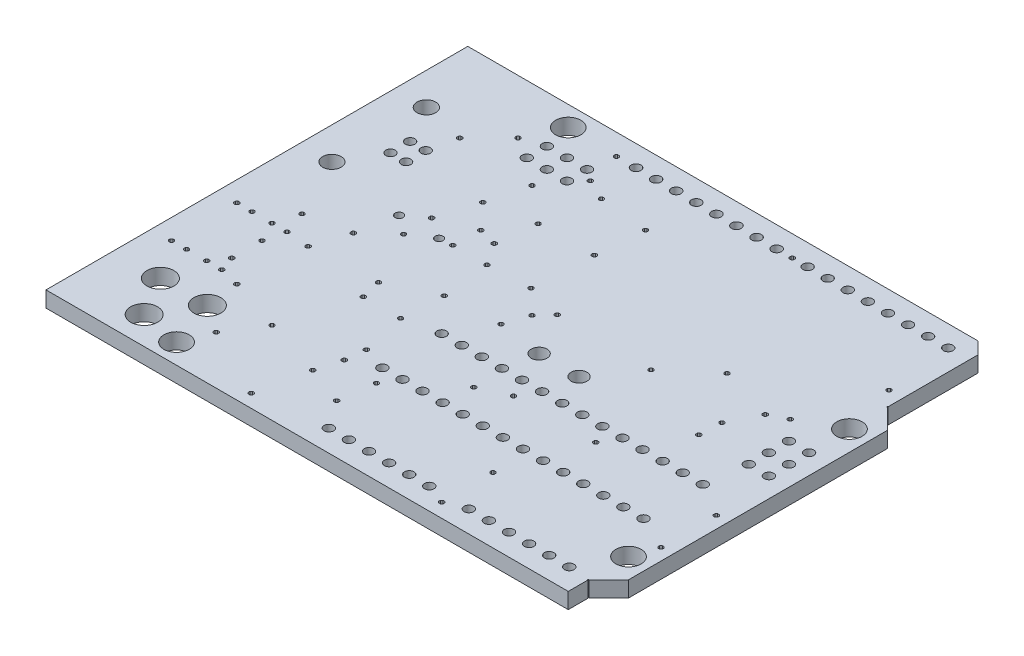
SolidWorks part; units mm, degrees
material "Fibra de vidrio-A"
ref_plane "Alzado" through (0, 0, 0) normal (0, 0, 1) x (1, 0, 0)
ref_plane "Planta" through (0, 0, 0) normal (0, 1, 0) x (1, 0, 0)
ref_plane "Vista lateral" through (0, 0, 0) normal (1, 0, 0) x (0, 0, -1)
sketch "Croquis1" plane through (0, 0, 0) normal (0, 1, 0) x (1, 0, 0)
  line L0 (0, 53.34) -> (64.516, 53.34)
  line L1 (64.516, 53.34) -> (66.04, 51.816)
  line L2 (66.04, 40.386) -> (68.58, 37.846)
  line L3 (68.58, 37.846) -> (68.58, 5.08)
  line L4 (68.58, 5.08) -> (66.04, 2.54)
  line L5 (66.04, 2.54) -> (66.04, 0)
  line L6 (66.04, 0) -> (0, 0)
  line L7 (0, 0) -> (0, 53.34)
  line L8 (66.04, 51.816) -> (66.04, 40.386)
  line L9 (30.8356, 10.5522) -> (30.8356, 10.7838)
  line L10 (30.8356, 10.7838) -> (30.9992, 10.9474)
  line L11 (30.9992, 10.9474) -> (31.2308, 10.9474)
  line L12 (31.2308, 10.9474) -> (31.3944, 10.7838)
  line L13 (31.3944, 10.7838) -> (31.3944, 10.5522)
  line L14 (31.3944, 10.5522) -> (31.2308, 10.3886)
  line L15 (31.2308, 10.3886) -> (30.9992, 10.3886)
  line L16 (30.9992, 10.3886) -> (30.8356, 10.5522)
  line L18 (25.2476, 19.1882) -> (25.2476, 19.4198)
  line L19 (25.2476, 19.4198) -> (25.4112, 19.5834)
  line L20 (25.4112, 19.5834) -> (25.6428, 19.5834)
  line L21 (25.6428, 19.5834) -> (25.8064, 19.4198)
  line L22 (25.8064, 19.4198) -> (25.8064, 19.1882)
  line L23 (25.8064, 19.1882) -> (25.6428, 19.0246)
  line L24 (25.6428, 19.0246) -> (25.4112, 19.0246)
  line L25 (25.4112, 19.0246) -> (25.2476, 19.1882)
  line L27 (7.5946, 24.3952) -> (7.5946, 24.6268)
  line L28 (7.5946, 24.6268) -> (7.7582, 24.7904)
  line L29 (7.7582, 24.7904) -> (7.9898, 24.7904)
  line L30 (7.9898, 24.7904) -> (8.1534, 24.6268)
  line L31 (8.1534, 24.6268) -> (8.1534, 24.3952)
  line L32 (8.1534, 24.3952) -> (7.9898, 24.2316)
  line L33 (7.9898, 24.2316) -> (7.7582, 24.2316)
  line L34 (7.7582, 24.2316) -> (7.5946, 24.3952)
  line L36 (26.2636, 11.0602) -> (26.2636, 11.2918)
  line L37 (26.2636, 11.2918) -> (26.4272, 11.4554)
  line L38 (26.4272, 11.4554) -> (26.6588, 11.4554)
  line L39 (26.6588, 11.4554) -> (26.8224, 11.2918)
  line L40 (26.8224, 11.2918) -> (26.8224, 11.0602)
  line L41 (26.8224, 11.0602) -> (26.6588, 10.8966)
  line L42 (26.6588, 10.8966) -> (26.4272, 10.8966)
  line L43 (26.4272, 10.8966) -> (26.2636, 11.0602)
  line L45 (17.8816, 10.2982) -> (17.8816, 10.5298)
  line L46 (17.8816, 10.5298) -> (18.0452, 10.6934)
  line L47 (18.0452, 10.6934) -> (18.2768, 10.6934)
  line L48 (18.2768, 10.6934) -> (18.4404, 10.5298)
  line L49 (18.4404, 10.5298) -> (18.4404, 10.2982)
  line L50 (18.4404, 10.2982) -> (18.2768, 10.1346)
  line L51 (18.2768, 10.1346) -> (18.0452, 10.1346)
  line L52 (18.0452, 10.1346) -> (17.8816, 10.2982)
  line L54 (2.2606, 21.4742) -> (2.2606, 21.7058)
  line L55 (2.2606, 21.7058) -> (2.4242, 21.8694)
  line L56 (2.4242, 21.8694) -> (2.6558, 21.8694)
  line L57 (2.6558, 21.8694) -> (2.8194, 21.7058)
  line L58 (2.8194, 21.7058) -> (2.8194, 21.4742)
  line L59 (2.8194, 21.4742) -> (2.6558, 21.3106)
  line L60 (2.6558, 21.3106) -> (2.4242, 21.3106)
  line L61 (2.4242, 21.3106) -> (2.2606, 21.4742)
  line L63 (4.1656, 21.4742) -> (4.1656, 21.7058)
  line L64 (4.1656, 21.7058) -> (4.3292, 21.8694)
  line L65 (4.3292, 21.8694) -> (4.5608, 21.8694)
  line L66 (4.5608, 21.8694) -> (4.7244, 21.7058)
  line L67 (4.7244, 21.7058) -> (4.7244, 21.4742)
  line L68 (4.7244, 21.4742) -> (4.5608, 21.3106)
  line L69 (4.5608, 21.3106) -> (4.3292, 21.3106)
  line L70 (4.3292, 21.3106) -> (4.1656, 21.4742)
  line L72 (6.7056, 21.4742) -> (6.7056, 21.7058)
  line L73 (6.7056, 21.7058) -> (6.8692, 21.8694)
  line L74 (6.8692, 21.8694) -> (7.1008, 21.8694)
  line L75 (7.1008, 21.8694) -> (7.2644, 21.7058)
  line L76 (7.2644, 21.7058) -> (7.2644, 21.4742)
  line L77 (7.2644, 21.4742) -> (7.1008, 21.3106)
  line L78 (7.1008, 21.3106) -> (6.8692, 21.3106)
  line L79 (6.8692, 21.3106) -> (6.7056, 21.4742)
  line L81 (8.6106, 21.4742) -> (8.6106, 21.7058)
  line L82 (8.6106, 21.7058) -> (8.7742, 21.8694)
  line L83 (8.7742, 21.8694) -> (9.0058, 21.8694)
  line L84 (9.0058, 21.8694) -> (9.1694, 21.7058)
  line L85 (9.1694, 21.7058) -> (9.1694, 21.4742)
  line L86 (9.1694, 21.4742) -> (9.0058, 21.3106)
  line L87 (9.0058, 21.3106) -> (8.7742, 21.3106)
  line L88 (8.7742, 21.3106) -> (8.6106, 21.4742)
  line L90 (2.2606, 13.2192) -> (2.2606, 13.4508)
  line L91 (2.2606, 13.4508) -> (2.4242, 13.6144)
  line L92 (2.4242, 13.6144) -> (2.6558, 13.6144)
  line L93 (2.6558, 13.6144) -> (2.8194, 13.4508)
  line L94 (2.8194, 13.4508) -> (2.8194, 13.2192)
  line L95 (2.8194, 13.2192) -> (2.6558, 13.0556)
  line L96 (2.6558, 13.0556) -> (2.4242, 13.0556)
  line L97 (2.4242, 13.0556) -> (2.2606, 13.2192)
  line L99 (4.1656, 13.2192) -> (4.1656, 13.4508)
  line L100 (4.1656, 13.4508) -> (4.3292, 13.6144)
  line L101 (4.3292, 13.6144) -> (4.5608, 13.6144)
  line L102 (4.5608, 13.6144) -> (4.7244, 13.4508)
  line L103 (4.7244, 13.4508) -> (4.7244, 13.2192)
  line L104 (4.7244, 13.2192) -> (4.5608, 13.0556)
  line L105 (4.5608, 13.0556) -> (4.3292, 13.0556)
  line L106 (4.3292, 13.0556) -> (4.1656, 13.2192)
  line L108 (6.7056, 13.2192) -> (6.7056, 13.4508)
  line L109 (6.7056, 13.4508) -> (6.8692, 13.6144)
  line L110 (6.8692, 13.6144) -> (7.1008, 13.6144)
  line L111 (7.1008, 13.6144) -> (7.2644, 13.4508)
  line L112 (7.2644, 13.4508) -> (7.2644, 13.2192)
  line L113 (7.2644, 13.2192) -> (7.1008, 13.0556)
  line L114 (7.1008, 13.0556) -> (6.8692, 13.0556)
  line L115 (6.8692, 13.0556) -> (6.7056, 13.2192)
  line L117 (8.6106, 13.2192) -> (8.6106, 13.4508)
  line L118 (8.6106, 13.4508) -> (8.7742, 13.6144)
  line L119 (8.7742, 13.6144) -> (9.0058, 13.6144)
  line L120 (9.0058, 13.6144) -> (9.1694, 13.4508)
  line L121 (9.1694, 13.4508) -> (9.1694, 13.2192)
  line L122 (9.1694, 13.2192) -> (9.0058, 13.0556)
  line L123 (9.0058, 13.0556) -> (8.7742, 13.0556)
  line L124 (8.7742, 13.0556) -> (8.6106, 13.2192)
  line L126 (7.9756, 15.1242) -> (7.9756, 15.3558)
  line L127 (7.9756, 15.3558) -> (8.1392, 15.5194)
  line L128 (8.1392, 15.5194) -> (8.3708, 15.5194)
  line L129 (8.3708, 15.5194) -> (8.5344, 15.3558)
  line L130 (8.5344, 15.3558) -> (8.5344, 15.1242)
  line L131 (8.5344, 15.1242) -> (8.3708, 14.9606)
  line L132 (8.3708, 14.9606) -> (8.1392, 14.9606)
  line L133 (8.1392, 14.9606) -> (7.9756, 15.1242)
  line L135 (7.9756, 18.9342) -> (7.9756, 19.1658)
  line L136 (7.9756, 19.1658) -> (8.1392, 19.3294)
  line L137 (8.1392, 19.3294) -> (8.3708, 19.3294)
  line L138 (8.3708, 19.3294) -> (8.5344, 19.1658)
  line L139 (8.5344, 19.1658) -> (8.5344, 18.9342)
  line L140 (8.5344, 18.9342) -> (8.3708, 18.7706)
  line L141 (8.3708, 18.7706) -> (8.1392, 18.7706)
  line L142 (8.1392, 18.7706) -> (7.9756, 18.9342)
  line L144 (20.6756, 33.9202) -> (20.6756, 34.1518)
  line L145 (20.6756, 34.1518) -> (20.8392, 34.3154)
  line L146 (20.8392, 34.3154) -> (21.0708, 34.3154)
  line L147 (21.0708, 34.3154) -> (21.2344, 34.1518)
  line L148 (21.2344, 34.1518) -> (21.2344, 33.9202)
  line L149 (21.2344, 33.9202) -> (21.0708, 33.7566)
  line L150 (21.0708, 33.7566) -> (20.8392, 33.7566)
  line L151 (20.8392, 33.7566) -> (20.6756, 33.9202)
  line L153 (24.8666, 44.9692) -> (24.8666, 45.2008)
  line L154 (24.8666, 45.2008) -> (25.0302, 45.3644)
  line L155 (25.0302, 45.3644) -> (25.2618, 45.3644)
  line L156 (25.2618, 45.3644) -> (25.4254, 45.2008)
  line L157 (25.4254, 45.2008) -> (25.4254, 44.9692)
  line L158 (25.4254, 44.9692) -> (25.2618, 44.8056)
  line L159 (25.2618, 44.8056) -> (25.0302, 44.8056)
  line L160 (25.0302, 44.8056) -> (24.8666, 44.9692)
  line L162 (23.5966, 38.2382) -> (23.5966, 38.4698)
  line L163 (23.5966, 38.4698) -> (23.7602, 38.6334)
  line L164 (23.7602, 38.6334) -> (23.9918, 38.6334)
  line L165 (23.9918, 38.6334) -> (24.1554, 38.4698)
  line L166 (24.1554, 38.4698) -> (24.1554, 38.2382)
  line L167 (24.1554, 38.2382) -> (23.9918, 38.0746)
  line L168 (23.9918, 38.0746) -> (23.7602, 38.0746)
  line L169 (23.7602, 38.0746) -> (23.5966, 38.2382)
  line L171 (24.8666, 30.4912) -> (24.8666, 30.7228)
  line L172 (24.8666, 30.7228) -> (25.0302, 30.8864)
  line L173 (25.0302, 30.8864) -> (25.2618, 30.8864)
  line L174 (25.2618, 30.8864) -> (25.4254, 30.7228)
  line L175 (25.4254, 30.7228) -> (25.4254, 30.4912)
  line L176 (25.4254, 30.4912) -> (25.2618, 30.3276)
  line L177 (25.2618, 30.3276) -> (25.0302, 30.3276)
  line L178 (25.0302, 30.3276) -> (24.8666, 30.4912)
  line L180 (20.5486, 19.1882) -> (20.5486, 19.4198)
  line L181 (20.5486, 19.4198) -> (20.7122, 19.5834)
  line L182 (20.7122, 19.5834) -> (20.9438, 19.5834)
  line L183 (20.9438, 19.5834) -> (21.1074, 19.4198)
  line L184 (21.1074, 19.4198) -> (21.1074, 19.1882)
  line L185 (21.1074, 19.1882) -> (20.9438, 19.0246)
  line L186 (20.9438, 19.0246) -> (20.7122, 19.0246)
  line L187 (20.7122, 19.0246) -> (20.5486, 19.1882)
  line L189 (11.5316, 21.2202) -> (11.5316, 21.4518)
  line L190 (11.5316, 21.4518) -> (11.6952, 21.6154)
  line L191 (11.6952, 21.6154) -> (11.9268, 21.6154)
  line L192 (11.9268, 21.6154) -> (12.0904, 21.4518)
  line L193 (12.0904, 21.4518) -> (12.0904, 21.2202)
  line L194 (12.0904, 21.2202) -> (11.9268, 21.0566)
  line L195 (11.9268, 21.0566) -> (11.6952, 21.0566)
  line L196 (11.6952, 21.0566) -> (11.5316, 21.2202)
  line L198 (30.226, 6.1326) -> (30.226, 6.3642)
  line L199 (30.226, 6.3642) -> (30.3896, 6.5278)
  line L200 (30.3896, 6.5278) -> (30.6212, 6.5278)
  line L201 (30.6212, 6.5278) -> (30.7848, 6.3642)
  line L202 (30.7848, 6.3642) -> (30.7848, 6.1326)
  line L203 (30.7848, 6.1326) -> (30.6212, 5.969)
  line L204 (30.6212, 5.969) -> (30.3896, 5.969)
  line L205 (30.3896, 5.969) -> (30.226, 6.1326)
  line L207 (26.5176, 13.6002) -> (26.5176, 13.8318)
  line L208 (26.5176, 13.8318) -> (26.6812, 13.9954)
  line L209 (26.6812, 13.9954) -> (26.9128, 13.9954)
  line L210 (26.9128, 13.9954) -> (27.0764, 13.8318)
  line L211 (27.0764, 13.8318) -> (27.0764, 13.6002)
  line L212 (27.0764, 13.6002) -> (26.9128, 13.4366)
  line L213 (26.9128, 13.4366) -> (26.6812, 13.4366)
  line L214 (26.6812, 13.4366) -> (26.5176, 13.6002)
  line L216 (17.7546, 37.0952) -> (17.7546, 37.3268)
  line L217 (17.7546, 37.3268) -> (17.9182, 37.4904)
  line L218 (17.9182, 37.4904) -> (18.1498, 37.4904)
  line L219 (18.1498, 37.4904) -> (18.3134, 37.3268)
  line L220 (18.3134, 37.3268) -> (18.3134, 37.0952)
  line L221 (18.3134, 37.0952) -> (18.1498, 36.9316)
  line L222 (18.1498, 36.9316) -> (17.9182, 36.9316)
  line L223 (17.9182, 36.9316) -> (17.7546, 37.0952)
  line L225 (20.5486, 30.4912) -> (20.5486, 30.7228)
  line L226 (20.5486, 30.7228) -> (20.7122, 30.8864)
  line L227 (20.7122, 30.8864) -> (20.9438, 30.8864)
  line L228 (20.9438, 30.8864) -> (21.1074, 30.7228)
  line L229 (21.1074, 30.7228) -> (21.1074, 30.4912)
  line L230 (21.1074, 30.4912) -> (20.9438, 30.3276)
  line L231 (20.9438, 30.3276) -> (20.7122, 30.3276)
  line L232 (20.7122, 30.3276) -> (20.5486, 30.4912)
  line L234 (15.113, 6.0056) -> (15.113, 6.2372)
  line L235 (15.113, 6.2372) -> (15.2766, 6.4008)
  line L236 (15.2766, 6.4008) -> (15.5082, 6.4008)
  line L237 (15.5082, 6.4008) -> (15.6718, 6.2372)
  line L238 (15.6718, 6.2372) -> (15.6718, 6.0056)
  line L239 (15.6718, 6.0056) -> (15.5082, 5.842)
  line L240 (15.5082, 5.842) -> (15.2766, 5.842)
  line L241 (15.2766, 5.842) -> (15.113, 6.0056)
  line L243 (22.987, 33.3106) -> (22.987, 33.5422)
  line L244 (22.987, 33.5422) -> (23.1506, 33.7058)
  line L245 (23.1506, 33.7058) -> (23.3822, 33.7058)
  line L246 (23.3822, 33.7058) -> (23.5458, 33.5422)
  line L247 (23.5458, 33.5422) -> (23.5458, 33.3106)
  line L248 (23.5458, 33.3106) -> (23.3822, 33.147)
  line L249 (23.3822, 33.147) -> (23.1506, 33.147)
  line L250 (23.1506, 33.147) -> (22.987, 33.3106)
  line L252 (51.9176, 33.7932) -> (51.9176, 34.0248)
  line L253 (51.9176, 34.0248) -> (52.0812, 34.1884)
  line L254 (52.0812, 34.1884) -> (52.3128, 34.1884)
  line L255 (52.3128, 34.1884) -> (52.4764, 34.0248)
  line L256 (52.4764, 34.0248) -> (52.4764, 33.7932)
  line L257 (52.4764, 33.7932) -> (52.3128, 33.6296)
  line L258 (52.3128, 33.6296) -> (52.0812, 33.6296)
  line L259 (52.0812, 33.6296) -> (51.9176, 33.7932)
  line L261 (30.5816, 38.3652) -> (30.5816, 38.5968)
  line L262 (30.5816, 38.5968) -> (30.7452, 38.7604)
  line L263 (30.7452, 38.7604) -> (30.9768, 38.7604)
  line L264 (30.9768, 38.7604) -> (31.1404, 38.5968)
  line L265 (31.1404, 38.5968) -> (31.1404, 38.3652)
  line L266 (31.1404, 38.3652) -> (30.9768, 38.2016)
  line L267 (30.9768, 38.2016) -> (30.7452, 38.2016)
  line L268 (30.7452, 38.2016) -> (30.5816, 38.3652)
  line L270 (11.1506, 12.5842) -> (11.1506, 12.8158)
  line L271 (11.1506, 12.8158) -> (11.3142, 12.9794)
  line L272 (11.3142, 12.9794) -> (11.5458, 12.9794)
  line L273 (11.5458, 12.9794) -> (11.7094, 12.8158)
  line L274 (11.7094, 12.8158) -> (11.7094, 12.5842)
  line L275 (11.7094, 12.5842) -> (11.5458, 12.4206)
  line L276 (11.5458, 12.4206) -> (11.3142, 12.4206)
  line L277 (11.3142, 12.4206) -> (11.1506, 12.5842)
  line L279 (40.894, 17.8166) -> (40.894, 18.0482)
  line L280 (40.894, 18.0482) -> (41.0576, 18.2118)
  line L281 (41.0576, 18.2118) -> (41.2892, 18.2118)
  line L282 (41.2892, 18.2118) -> (41.4528, 18.0482)
  line L283 (41.4528, 18.0482) -> (41.4528, 17.8166)
  line L284 (41.4528, 17.8166) -> (41.2892, 17.653)
  line L285 (41.2892, 17.653) -> (41.0576, 17.653)
  line L286 (41.0576, 17.653) -> (40.894, 17.8166)
  line L288 (51.181, 17.9436) -> (51.181, 18.1752)
  line L289 (51.181, 18.1752) -> (51.3446, 18.3388)
  line L290 (51.3446, 18.3388) -> (51.5762, 18.3388)
  line L291 (51.5762, 18.3388) -> (51.7398, 18.1752)
  line L292 (51.7398, 18.1752) -> (51.7398, 17.9436)
  line L293 (51.7398, 17.9436) -> (51.5762, 17.78)
  line L294 (51.5762, 17.78) -> (51.3446, 17.78)
  line L295 (51.3446, 17.78) -> (51.181, 17.9436)
  line L297 (30.2006, 30.7452) -> (30.2006, 30.9768)
  line L298 (30.2006, 30.9768) -> (30.3642, 31.1404)
  line L299 (30.3642, 31.1404) -> (30.5958, 31.1404)
  line L300 (30.5958, 31.1404) -> (30.7594, 30.9768)
  line L301 (30.7594, 30.9768) -> (30.7594, 30.7452)
  line L302 (30.7594, 30.7452) -> (30.5958, 30.5816)
  line L303 (30.5958, 30.5816) -> (30.3642, 30.5816)
  line L304 (30.3642, 30.5816) -> (30.2006, 30.7452)
  line L306 (43.4086, 50.5572) -> (43.4086, 50.7888)
  line L307 (43.4086, 50.7888) -> (43.5722, 50.9524)
  line L308 (43.5722, 50.9524) -> (43.8038, 50.9524)
  line L309 (43.8038, 50.9524) -> (43.9674, 50.7888)
  line L310 (43.9674, 50.7888) -> (43.9674, 50.5572)
  line L311 (43.9674, 50.5572) -> (43.8038, 50.3936)
  line L312 (43.8038, 50.3936) -> (43.5722, 50.3936)
  line L313 (43.5722, 50.3936) -> (43.4086, 50.5572)
  line L315 (47.9806, 1.6622) -> (47.9806, 1.8938)
  line L316 (47.9806, 1.8938) -> (48.1442, 2.0574)
  line L317 (48.1442, 2.0574) -> (48.3758, 2.0574)
  line L318 (48.3758, 2.0574) -> (48.5394, 1.8938)
  line L319 (48.5394, 1.8938) -> (48.5394, 1.6622)
  line L320 (48.5394, 1.6622) -> (48.3758, 1.4986)
  line L321 (48.3758, 1.4986) -> (48.1442, 1.4986)
  line L322 (48.1442, 1.4986) -> (47.9806, 1.6622)
  line L324 (16.2306, 28.5862) -> (16.2306, 28.8178)
  line L325 (16.2306, 28.8178) -> (16.3942, 28.9814)
  line L326 (16.3942, 28.9814) -> (16.6258, 28.9814)
  line L327 (16.6258, 28.9814) -> (16.7894, 28.8178)
  line L328 (16.7894, 28.8178) -> (16.7894, 28.5862)
  line L329 (16.7894, 28.5862) -> (16.6258, 28.4226)
  line L330 (16.6258, 28.4226) -> (16.3942, 28.4226)
  line L331 (16.3942, 28.4226) -> (16.2306, 28.5862)
  line L333 (56.9976, 28.0782) -> (56.9976, 28.3098)
  line L334 (56.9976, 28.3098) -> (57.1612, 28.4734)
  line L335 (57.1612, 28.4734) -> (57.3928, 28.4734)
  line L336 (57.3928, 28.4734) -> (57.5564, 28.3098)
  line L337 (57.5564, 28.3098) -> (57.5564, 28.0782)
  line L338 (57.5564, 28.0782) -> (57.3928, 27.9146)
  line L339 (57.3928, 27.9146) -> (57.1612, 27.9146)
  line L340 (57.1612, 27.9146) -> (56.9976, 28.0782)
  line L342 (24.003, 1.5606) -> (24.003, 1.7922)
  line L343 (24.003, 1.7922) -> (24.1666, 1.9558)
  line L344 (24.1666, 1.9558) -> (24.3982, 1.9558)
  line L345 (24.3982, 1.9558) -> (24.5618, 1.7922)
  line L346 (24.5618, 1.7922) -> (24.5618, 1.5606)
  line L347 (24.5618, 1.5606) -> (24.3982, 1.397)
  line L348 (24.3982, 1.397) -> (24.1666, 1.397)
  line L349 (24.1666, 1.397) -> (24.003, 1.5606)
  line L351 (66.802, 10.5776) -> (66.802, 10.8092)
  line L352 (66.802, 10.8092) -> (66.9656, 10.9728)
  line L353 (66.9656, 10.9728) -> (67.1972, 10.9728)
  line L354 (67.1972, 10.9728) -> (67.3608, 10.8092)
  line L355 (67.3608, 10.8092) -> (67.3608, 10.5776)
  line L356 (67.3608, 10.5776) -> (67.1972, 10.414)
  line L357 (67.1972, 10.414) -> (66.9656, 10.414)
  line L358 (66.9656, 10.414) -> (66.802, 10.5776)
  line L360 (64.008, 42.2006) -> (64.008, 42.4322)
  line L361 (64.008, 42.4322) -> (64.1716, 42.5958)
  line L362 (64.1716, 42.5958) -> (64.4032, 42.5958)
  line L363 (64.4032, 42.5958) -> (64.5668, 42.4322)
  line L364 (64.5668, 42.4322) -> (64.5668, 42.2006)
  line L365 (64.5668, 42.2006) -> (64.4032, 42.037)
  line L366 (64.4032, 42.037) -> (64.1716, 42.037)
  line L367 (64.1716, 42.037) -> (64.008, 42.2006)
  line L369 (12.9286, 25.5382) -> (12.9286, 25.7698)
  line L370 (12.9286, 25.7698) -> (13.0922, 25.9334)
  line L371 (13.0922, 25.9334) -> (13.3238, 25.9334)
  line L372 (13.3238, 25.9334) -> (13.4874, 25.7698)
  line L373 (13.4874, 25.7698) -> (13.4874, 25.5382)
  line L374 (13.4874, 25.5382) -> (13.3238, 25.3746)
  line L375 (13.3238, 25.3746) -> (13.0922, 25.3746)
  line L376 (13.0922, 25.3746) -> (12.9286, 25.5382)
  line L378 (66.802, 17.5626) -> (66.802, 17.7942)
  line L379 (66.802, 17.7942) -> (66.9656, 17.9578)
  line L380 (66.9656, 17.9578) -> (67.1972, 17.9578)
  line L381 (67.1972, 17.9578) -> (67.3608, 17.7942)
  line L382 (67.3608, 17.7942) -> (67.3608, 17.5626)
  line L383 (67.3608, 17.5626) -> (67.1972, 17.399)
  line L384 (67.1972, 17.399) -> (66.9656, 17.399)
  line L385 (66.9656, 17.399) -> (66.802, 17.5626)
  line L387 (19.9136, 21.7282) -> (19.9136, 21.9598)
  line L388 (19.9136, 21.9598) -> (20.0772, 22.1234)
  line L389 (20.0772, 22.1234) -> (20.3088, 22.1234)
  line L390 (20.3088, 22.1234) -> (20.4724, 21.9598)
  line L391 (20.4724, 21.9598) -> (20.4724, 21.7282)
  line L392 (20.4724, 21.7282) -> (20.3088, 21.5646)
  line L393 (20.3088, 21.5646) -> (20.0772, 21.5646)
  line L394 (20.0772, 21.5646) -> (19.9136, 21.7282)
  line L396 (12.9286, 46.3662) -> (12.9286, 46.5978)
  line L397 (12.9286, 46.5978) -> (13.0922, 46.7614)
  line L398 (13.0922, 46.7614) -> (13.3238, 46.7614)
  line L399 (13.3238, 46.7614) -> (13.4874, 46.5978)
  line L400 (13.4874, 46.5978) -> (13.4874, 46.3662)
  line L401 (13.4874, 46.3662) -> (13.3238, 46.2026)
  line L402 (13.3238, 46.2026) -> (13.0922, 46.2026)
  line L403 (13.0922, 46.2026) -> (12.9286, 46.3662)
  line L405 (21.1836, 50.5572) -> (21.1836, 50.7888)
  line L406 (21.1836, 50.7888) -> (21.3472, 50.9524)
  line L407 (21.3472, 50.9524) -> (21.5788, 50.9524)
  line L408 (21.5788, 50.9524) -> (21.7424, 50.7888)
  line L409 (21.7424, 50.7888) -> (21.7424, 50.5572)
  line L410 (21.7424, 50.5572) -> (21.5788, 50.3936)
  line L411 (21.5788, 50.3936) -> (21.3472, 50.3936)
  line L412 (21.3472, 50.3936) -> (21.1836, 50.5572)
  line L414 (46.736, 29.3736) -> (46.736, 29.6052)
  line L415 (46.736, 29.6052) -> (46.8996, 29.7688)
  line L416 (46.8996, 29.7688) -> (47.1312, 29.7688)
  line L417 (47.1312, 29.7688) -> (47.2948, 29.6052)
  line L418 (47.2948, 29.6052) -> (47.2948, 29.3736)
  line L419 (47.2948, 29.3736) -> (47.1312, 29.21)
  line L420 (47.1312, 29.21) -> (46.8996, 29.21)
  line L421 (46.8996, 29.21) -> (46.736, 29.3736)
  line L423 (16.2306, 32.1422) -> (16.2306, 32.3738)
  line L424 (16.2306, 32.3738) -> (16.3942, 32.5374)
  line L425 (16.3942, 32.5374) -> (16.6258, 32.5374)
  line L426 (16.6258, 32.5374) -> (16.7894, 32.3738)
  line L427 (16.7894, 32.3738) -> (16.7894, 32.1422)
  line L428 (16.7894, 32.1422) -> (16.6258, 31.9786)
  line L429 (16.6258, 31.9786) -> (16.3942, 31.9786)
  line L430 (16.3942, 31.9786) -> (16.2306, 32.1422)
  line L432 (60.9346, 32.7772) -> (60.9346, 33.0088)
  line L433 (60.9346, 33.0088) -> (61.0982, 33.1724)
  line L434 (61.0982, 33.1724) -> (61.3298, 33.1724)
  line L435 (61.3298, 33.1724) -> (61.4934, 33.0088)
  line L436 (61.4934, 33.0088) -> (61.4934, 32.7772)
  line L437 (61.4934, 32.7772) -> (61.3298, 32.6136)
  line L438 (61.3298, 32.6136) -> (61.0982, 32.6136)
  line L439 (61.0982, 32.6136) -> (60.9346, 32.7772)
  line L441 (58.8518, 31.7104) -> (58.8518, 31.942)
  line L442 (58.8518, 31.942) -> (59.0154, 32.1056)
  line L443 (59.0154, 32.1056) -> (59.247, 32.1056)
  line L444 (59.247, 32.1056) -> (59.4106, 31.942)
  line L445 (59.4106, 31.942) -> (59.4106, 31.7104)
  line L446 (59.4106, 31.7104) -> (59.247, 31.5468)
  line L447 (59.247, 31.5468) -> (59.0154, 31.5468)
  line L448 (59.0154, 31.5468) -> (58.8518, 31.7104)
  line L450 (32.2326, 24.9032) -> (32.2326, 25.1348)
  line L451 (32.2326, 25.1348) -> (32.3962, 25.2984)
  line L452 (32.3962, 25.2984) -> (32.6278, 25.2984)
  line L453 (32.6278, 25.2984) -> (32.7914, 25.1348)
  line L454 (32.7914, 25.1348) -> (32.7914, 24.9032)
  line L455 (32.7914, 24.9032) -> (32.6278, 24.7396)
  line L456 (32.6278, 24.7396) -> (32.3962, 24.7396)
  line L457 (32.3962, 24.7396) -> (32.2326, 24.9032)
  line L459 (37.4396, 16.2672) -> (37.4396, 16.4988)
  line L460 (37.4396, 16.4988) -> (37.6032, 16.6624)
  line L461 (37.6032, 16.6624) -> (37.8348, 16.6624)
  line L462 (37.8348, 16.6624) -> (37.9984, 16.4988)
  line L463 (37.9984, 16.4988) -> (37.9984, 16.2672)
  line L464 (37.9984, 16.2672) -> (37.8348, 16.1036)
  line L465 (37.8348, 16.1036) -> (37.6032, 16.1036)
  line L466 (37.6032, 16.1036) -> (37.4396, 16.2672)
  line L468 (19.0246, 42.0482) -> (19.0246, 42.2798)
  line L469 (19.0246, 42.2798) -> (19.1882, 42.4434)
  line L470 (19.1882, 42.4434) -> (19.4198, 42.4434)
  line L471 (19.4198, 42.4434) -> (19.5834, 42.2798)
  line L472 (19.5834, 42.2798) -> (19.5834, 42.0482)
  line L473 (19.5834, 42.0482) -> (19.4198, 41.8846)
  line L474 (19.4198, 41.8846) -> (19.1882, 41.8846)
  line L475 (19.1882, 41.8846) -> (19.0246, 42.0482)
  line L477 (34.7726, 29.4752) -> (34.7726, 29.7068)
  line L478 (34.7726, 29.7068) -> (34.9362, 29.8704)
  line L479 (34.9362, 29.8704) -> (35.1678, 29.8704)
  line L480 (35.1678, 29.8704) -> (35.3314, 29.7068)
  line L481 (35.3314, 29.7068) -> (35.3314, 29.4752)
  line L482 (35.3314, 29.4752) -> (35.1678, 29.3116)
  line L483 (35.1678, 29.3116) -> (34.9362, 29.3116)
  line L484 (34.9362, 29.3116) -> (34.7726, 29.4752)
  line L486 (56.8706, 25.2842) -> (56.8706, 25.5158)
  line L487 (56.8706, 25.5158) -> (57.0342, 25.6794)
  line L488 (57.0342, 25.6794) -> (57.2658, 25.6794)
  line L489 (57.2658, 25.6794) -> (57.4294, 25.5158)
  line L490 (57.4294, 25.5158) -> (57.4294, 25.2842)
  line L491 (57.4294, 25.2842) -> (57.2658, 25.1206)
  line L492 (57.2658, 25.1206) -> (57.0342, 25.1206)
  line L493 (57.0342, 25.1206) -> (56.8706, 25.2842)
  line L495 (25.5524, 24.4206) -> (25.5524, 24.6522)
  line L496 (25.5524, 24.6522) -> (25.716, 24.8158)
  line L497 (25.716, 24.8158) -> (25.9476, 24.8158)
  line L498 (25.9476, 24.8158) -> (26.1112, 24.6522)
  line L499 (26.1112, 24.6522) -> (26.1112, 24.4206)
  line L500 (26.1112, 24.4206) -> (25.9476, 24.257)
  line L501 (25.9476, 24.257) -> (25.716, 24.257)
  line L502 (25.716, 24.257) -> (25.5524, 24.4206)
  line L504 (22.1996, 46.2392) -> (22.1996, 46.4708)
  line L505 (22.1996, 46.4708) -> (22.3632, 46.6344)
  line L506 (22.3632, 46.6344) -> (22.5948, 46.6344)
  line L507 (22.5948, 46.6344) -> (22.7584, 46.4708)
  line L508 (22.7584, 46.4708) -> (22.7584, 46.2392)
  line L509 (22.7584, 46.2392) -> (22.5948, 46.0756)
  line L510 (22.5948, 46.0756) -> (22.3632, 46.0756)
  line L511 (22.3632, 46.0756) -> (22.1996, 46.2392)
  line L513 (31.0896, 44.3342) -> (31.0896, 44.5658)
  line L514 (31.0896, 44.5658) -> (31.2532, 44.7294)
  line L515 (31.2532, 44.7294) -> (31.4848, 44.7294)
  line L516 (31.4848, 44.7294) -> (31.6484, 44.5658)
  line L517 (31.6484, 44.5658) -> (31.6484, 44.3342)
  line L518 (31.6484, 44.3342) -> (31.4848, 44.1706)
  line L519 (31.4848, 44.1706) -> (31.2532, 44.1706)
  line L520 (31.2532, 44.1706) -> (31.0896, 44.3342)
  line L522 (33.2486, 27.8242) -> (33.2486, 28.0558)
  line L523 (33.2486, 28.0558) -> (33.4122, 28.2194)
  line L524 (33.4122, 28.2194) -> (33.6438, 28.2194)
  line L525 (33.6438, 28.2194) -> (33.8074, 28.0558)
  line L526 (33.8074, 28.0558) -> (33.8074, 27.8242)
  line L527 (33.8074, 27.8242) -> (33.6438, 27.6606)
  line L528 (33.6438, 27.6606) -> (33.4122, 27.6606)
  line L529 (33.4122, 27.6606) -> (33.2486, 27.8242)
  line L531 (9.2456, 42.6832) -> (9.2456, 42.9148)
  line L532 (9.2456, 42.9148) -> (9.4092, 43.0784)
  line L533 (9.4092, 43.0784) -> (9.6408, 43.0784)
  line L534 (9.6408, 43.0784) -> (9.8044, 42.9148)
  line L535 (9.8044, 42.9148) -> (9.8044, 42.6832)
  line L536 (9.8044, 42.6832) -> (9.6408, 42.5196)
  line L537 (9.6408, 42.5196) -> (9.4092, 42.5196)
  line L538 (9.4092, 42.5196) -> (9.2456, 42.6832)
  line L540 (25.3746, 7.9614) -> (25.3746, 8.193)
  line L541 (25.3746, 8.193) -> (25.5382, 8.3566)
  line L542 (25.5382, 8.3566) -> (25.7698, 8.3566)
  line L543 (25.7698, 8.3566) -> (25.9334, 8.193)
  line L544 (25.9334, 8.193) -> (25.9334, 7.9614)
  line L545 (25.9334, 7.9614) -> (25.7698, 7.7978)
  line L546 (25.7698, 7.7978) -> (25.5382, 7.7978)
  line L547 (25.5382, 7.7978) -> (25.3746, 7.9614)
  line L549 (47.9806, 8.1392) -> (47.9806, 8.3708)
  line L550 (47.9806, 8.3708) -> (48.1442, 8.5344)
  line L551 (48.1442, 8.5344) -> (48.3758, 8.5344)
  line L552 (48.3758, 8.5344) -> (48.5394, 8.3708)
  line L553 (48.5394, 8.3708) -> (48.5394, 8.1392)
  line L554 (48.5394, 8.1392) -> (48.3758, 7.9756)
  line L555 (48.3758, 7.9756) -> (48.1442, 7.9756)
  line L556 (48.1442, 7.9756) -> (47.9806, 8.1392)
  arc A0 (64.516, 53.2765) -> (64.4711, 53.2951) centre (64.516, 53.34) ccw
  arc A1 (0.0635, 53.34) -> (0, 53.2765) centre (0, 53.34) ccw
  arc A2 (65.9951, 51.7711) -> (65.9765, 51.816) centre (66.04, 51.816) ccw
  arc A3 (68.5351, 37.8011) -> (68.5165, 37.846) centre (68.58, 37.846) ccw
  arc A4 (66.0849, 40.4309) -> (66.1035, 40.386) centre (66.04, 40.386) ccw
  arc A5 (68.5165, 5.08) -> (68.5351, 5.1249) centre (68.58, 5.08) ccw
  arc A6 (66.1035, 2.54) -> (66.0849, 2.4951) centre (66.04, 2.54) ccw
  arc A7 (65.9765, 0) -> (66.04, 0.0635) centre (66.04, 0) ccw
  arc A8 (0, 0.0635) -> (0.0635, 0) centre (0, 0) ccw
  circle A18 centre (66.04, 35.56) radius 1.6
  circle A19 centre (66.04, 7.62) radius 1.6
  circle A20 centre (15.24, 50.8) radius 1.6
  circle A21 centre (13.97, 2.54) radius 1.6
extrude "Saliente-Extruir1" add sketch "Croquis1" along normal blind 2 contours L8 L1 L0 L7 L6 L5 L4 L3 L2 A21 A20 A19 region at (33.8305, 0, -26.5617)
sketch "Croquis4" plane through (0, 2, 0) normal (0, 1, 0) x (1, 0, 0)
  circle A0 centre (63.4055, 50.6844) radius 0.5997
  circle A1 centre (60.8655, 50.6844) radius 0.5997
  circle A2 centre (58.3255, 50.6844) radius 0.5997
  circle A3 centre (55.7855, 50.6844) radius 0.5997
  circle A4 centre (53.2455, 50.6844) radius 0.5997
  circle A5 centre (50.7055, 50.6844) radius 0.5997
  circle A6 centre (48.1655, 50.6844) radius 0.5997
  circle A7 centre (45.6255, 50.6844) radius 0.5997
  circle A8 centre (41.708, 50.6844) radius 0.6076
  circle A9 centre (39.168, 50.6844) radius 0.6076
  circle A10 centre (36.628, 50.6844) radius 0.6076
  circle A11 centre (34.088, 50.6844) radius 0.6076
  circle A12 centre (31.548, 50.6844) radius 0.6076
  circle A13 centre (29.008, 50.6844) radius 0.6076
  circle A14 centre (26.468, 50.6844) radius 0.6076
  circle A15 centre (23.928, 50.6844) radius 0.6076
  circle A16 centre (4.0615, 44.0362) radius 1.1759
  circle A17 centre (15.94, 47.399) radius 0.5985
  circle A18 centre (18.48, 47.399) radius 0.5985
  circle A19 centre (21.02, 47.399) radius 0.5985
  circle A20 centre (15.94, 44.859) radius 0.5985
  circle A21 centre (18.48, 44.859) radius 0.5985
  circle A22 centre (21.02, 44.859) radius 0.5985
  circle A23 centre (6.771, 39.274) radius 0.6
  circle A24 centre (8.743, 39.274) radius 0.6
  circle A25 centre (6.771, 36.79) radius 0.6
  circle A26 centre (8.743, 36.79) radius 0.6
  circle A27 centre (4.0615, 32.0963) radius 1.17
  circle A28 centre (8.9039, 3.5064) radius 1.7
  circle A29 centre (5.9634, 8.5052) radius 1.7
  circle A30 centre (11.8986, 8.5052) radius 1.7
  circle A31 centre (62.8267, 20.2292) radius 0.6
  circle A32 centre (60.2867, 20.2292) radius 0.6
  circle A33 centre (57.7467, 20.2292) radius 0.6
  circle A34 centre (55.2067, 20.2292) radius 0.6
  circle A35 centre (52.6667, 20.2292) radius 0.6
  circle A36 centre (50.1267, 20.2292) radius 0.6
  circle A37 centre (47.5867, 20.2292) radius 0.6
  circle A38 centre (45.0467, 20.2292) radius 0.6
  circle A39 centre (42.5067, 20.2292) radius 0.6
  circle A40 centre (39.9667, 20.2292) radius 0.6
  circle A41 centre (37.4267, 20.2292) radius 0.6
  circle A42 centre (34.8867, 20.2292) radius 0.6
  circle A43 centre (32.3467, 20.2292) radius 0.6
  circle A44 centre (29.8067, 20.2292) radius 0.6
  circle A45 centre (62.8267, 12.7292) radius 0.6
  circle A46 centre (60.2867, 12.7292) radius 0.6
  circle A47 centre (57.7467, 12.7292) radius 0.6
  circle A48 centre (55.2067, 12.7292) radius 0.6
  circle A49 centre (52.6667, 12.7292) radius 0.6
  circle A50 centre (50.1267, 12.7292) radius 0.6
  circle A51 centre (47.5867, 12.7292) radius 0.6
  circle A52 centre (45.0467, 12.7292) radius 0.6
  circle A53 centre (42.5067, 12.7292) radius 0.6
  circle A54 centre (39.9667, 12.7292) radius 0.6
  circle A55 centre (37.4267, 12.7292) radius 0.6
  circle A56 centre (34.8867, 12.7292) radius 0.6
  circle A57 centre (32.3467, 12.7292) radius 0.6
  circle A58 centre (29.8067, 12.7292) radius 0.6
  circle A59 centre (63.4267, 2.7437) radius 0.6
  circle A60 centre (60.8867, 2.7437) radius 0.6
  circle A61 centre (58.3467, 2.7437) radius 0.6
  circle A62 centre (55.8067, 2.7437) radius 0.6
  circle A63 centre (53.2667, 2.7437) radius 0.6
  circle A64 centre (50.7267, 2.7437) radius 0.6
  circle A65 centre (45.7241, 2.7437) radius 0.6
  circle A66 centre (43.1841, 2.7437) radius 0.6
  circle A67 centre (40.6441, 2.7437) radius 0.6
  circle A68 centre (38.1041, 2.7437) radius 0.6
  circle A69 centre (35.5641, 2.7437) radius 0.6
  circle A70 centre (33.0241, 2.7437) radius 0.6
  circle A71 centre (66.0817, 30.4115) radius 0.6
  circle A72 centre (63.5417, 30.4115) radius 0.6
  circle A73 centre (66.0817, 27.8715) radius 0.6
  circle A74 centre (63.5417, 27.8715) radius 0.6
  circle A75 centre (66.0817, 25.3315) radius 0.6
  circle A76 centre (63.5417, 25.3315) radius 0.6
  circle A77 centre (38.1583, 24.1945) radius 1.0021
  circle A78 centre (43.2109, 24.1945) radius 0.9964
  circle A79 centre (14.1599, 30.4893) radius 0.5
  circle A80 centre (19.2167, 30.4893) radius 0.5
  dimension "D5" = 14
  dimension "D7" = 6
  dimension "D8" = 6
  dimension "D9" = 2
  dimension "D1" = 8
  dimension "D2" = 8
  dimension "D3" = 3
  dimension "D4" = 2
  dimension "D6" = 2
  dimension "D10" = 3
extrude "Cortar-Extruir2" cut sketch "Croquis4" against normal up to surface (2 mm away) up to face at (54.3494, 0, -26.1158)
